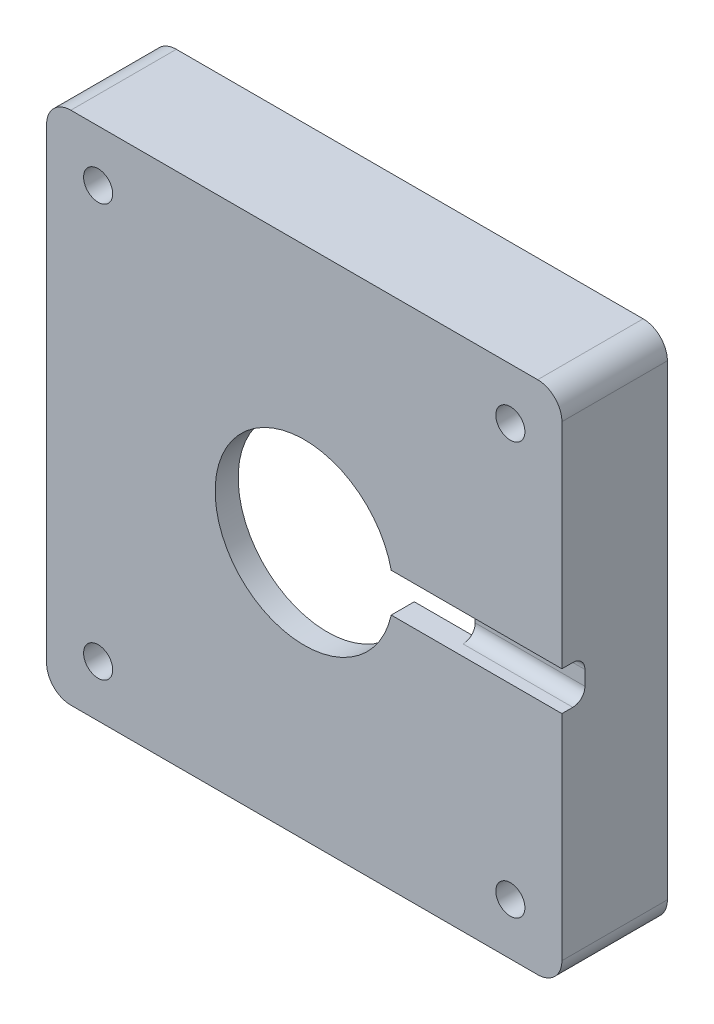
SolidWorks part; units mm, degrees
ref_plane "Front Plane" through (0, 0, 0) normal (0, 0, 1) x (1, 0, 0)
ref_plane "Top Plane" through (0, 0, 0) normal (0, 1, 0) x (1, 0, 0)
ref_plane "Right Plane" through (0, 0, 0) normal (1, 0, 0) x (0, 0, -1)
sketch "Sketch1" plane through (0, 0, 0) normal (0, 0, 1) x (1, 0, 0)
  line L0 (21.25, -19.25) -> (21.25, 19.25) construction
  line L1 (-19.25, -21.25) -> (19.25, -21.25) construction
  line L2 (-21.25, 19.25) -> (-21.25, -19.25) construction
  line L3 (19.25, 21.25) -> (-19.25, 21.25) construction
  line L4 (21.25, -19.25) -> (21.25, 19.25)
  line L5 (-19.25, -21.25) -> (19.25, -21.25)
  line L6 (-21.25, 19.25) -> (-21.25, -19.25)
  line L7 (19.25, 21.25) -> (-19.25, 21.25)
  arc A0 (21.25, 19.25) -> (19.25, 21.25) centre (19.25, 19.25) ccw construction
  arc A1 (19.25, -21.25) -> (21.25, -19.25) centre (19.25, -19.25) ccw construction
  arc A2 (-21.25, -19.25) -> (-19.25, -21.25) centre (-19.25, -19.25) ccw construction
  arc A3 (-19.25, 21.25) -> (-21.25, 19.25) centre (-19.25, 19.25) ccw construction
  arc A4 (21.25, 19.25) -> (19.25, 21.25) centre (19.25, 19.25) ccw
  arc A5 (19.25, -21.25) -> (21.25, -19.25) centre (19.25, -19.25) ccw
  arc A6 (-21.25, -19.25) -> (-19.25, -21.25) centre (-19.25, -19.25) ccw
  arc A7 (-19.25, 21.25) -> (-21.25, 19.25) centre (-19.25, 19.25) ccw
  circle A8 centre (-17, -17) radius 1.2 construction
  circle A9 centre (17, -17) radius 1.2 construction
  circle A10 centre (17, 17) radius 1.2 construction
  circle A11 centre (-17, 17) radius 1.2 construction
  circle A12 centre (-17, -17) radius 1.2
  circle A13 centre (17, -17) radius 1.2
  circle A14 centre (17, 17) radius 1.2
  circle A15 centre (-17, 17) radius 1.2
  point P37 (0.1087, 0)
  point P38 (0, 0)
  point P39 (21.25, 1.6)
extrude "Boss-Extrude1" add sketch "Sketch1" along normal offset from surface (8.7 mm away) 2 offset beyond the face yes
sketch "Sketch2" plane through (0, 0, 0) normal (0, 0, -1) x (-1, 0, 0)
  line L0 (19.25, -19.25) -> (-19.25, -19.25) construction
  line L2 (-19.25, 19.25) -> (19.25, 19.25) construction
  line L3 (19.25, 19.25) -> (19.25, -19.25) construction
  line L4 (17, 14.55) -> (19.25, 14.55) construction
  line L5 (14.55, 19.25) -> (14.55, 17) construction
  line L6 (-14.55, 17) -> (-14.55, 19.25) construction
  line L7 (-19.25, 14.55) -> (-17, 14.55) construction
  line L8 (-14.55, -19.25) -> (-14.55, -17) construction
  line L9 (-17, -14.55) -> (-19.25, -14.55) construction
  line L10 (19.25, -14.55) -> (17, -14.55) construction
  line L11 (14.55, -17) -> (14.55, -19.25) construction
  line L12 (14.55, -19.25) -> (-14.55, -19.25)
  line L13 (-19.25, -14.55) -> (-19.25, 14.55)
  line L14 (-14.55, 19.25) -> (14.55, 19.25)
  line L15 (19.25, 14.55) -> (19.25, -14.55)
  line L16 (17, 14.55) -> (19.25, 14.55)
  line L17 (14.55, 19.25) -> (14.55, 17)
  line L18 (-14.55, 17) -> (-14.55, 19.25)
  line L19 (-19.25, 14.55) -> (-17, 14.55)
  line L20 (-14.55, -19.25) -> (-14.55, -17)
  line L21 (-17, -14.55) -> (-19.25, -14.55)
  line L22 (19.25, -14.55) -> (17, -14.55)
  line L23 (14.55, -17) -> (14.55, -19.25)
  arc A0 (14.55, 17) -> (17, 14.55) centre (17, 17) ccw construction
  arc A1 (-17, 14.55) -> (-14.55, 17) centre (-17, 17) ccw construction
  arc A2 (-14.55, -17) -> (-17, -14.55) centre (-17, -17) ccw construction
  arc A3 (17, -14.55) -> (14.55, -17) centre (17, -17) ccw construction
  arc A4 (14.55, 17) -> (17, 14.55) centre (17, 17) ccw
  arc A5 (-17, 14.55) -> (-14.55, 17) centre (-17, 17) ccw
  arc A6 (-14.55, -17) -> (-17, -14.55) centre (-17, -17) ccw
  arc A7 (17, -14.55) -> (14.55, -17) centre (17, -17) ccw
extrude "Cut-Extrude2" cut sketch "Sketch2" against normal blind 3
sketch "Sketch3" plane through (0, 0, 3) normal (0, 0, -1) x (-1, 0, 0)
  line L0 (-12, -6) -> (-12, 6) construction
  line L1 (5, -13) -> (-5, -13) construction
  line L2 (12, 6) -> (12, -6) construction
  line L3 (-5, 13) -> (5, 13) construction
  line L4 (-12, -6) -> (-12, 6) construction
  line L5 (5, -13) -> (-5, -13) construction
  line L6 (12, 6) -> (12, -6) construction
  line L7 (-5, 13) -> (5, 13) construction
  line L8 (-12.2, -6) -> (-12.2, 6)
  line L9 (-5, 13.2) -> (5, 13.2)
  line L10 (12.2, 6) -> (12.2, -6)
  line L11 (5, -13.2) -> (-5, -13.2)
  arc A0 (-5, 13) -> (-12, 6) centre (-5, 6) ccw construction
  arc A1 (-12, -6) -> (-5, -13) centre (-5, -6) ccw construction
  arc A2 (5, -13) -> (12, -6) centre (5, -6) ccw construction
  arc A3 (12, 6) -> (5, 13) centre (5, 6) ccw construction
  arc A4 (-5, 13) -> (-12, 6) centre (-5, 6) ccw construction
  arc A5 (-12, -6) -> (-5, -13) centre (-5, -6) ccw construction
  arc A6 (5, -13) -> (12, -6) centre (5, -6) ccw construction
  arc A7 (12, 6) -> (5, 13) centre (5, 6) ccw construction
  arc A8 (-5, 13.2) -> (-12.2, 6) centre (-5, 6) ccw
  arc A9 (12.2, 6) -> (5, 13.2) centre (5, 6) ccw
  arc A10 (5, -13.2) -> (12.2, -6) centre (5, -6) ccw
  arc A11 (-12.2, -6) -> (-5, -13.2) centre (-5, -6) ccw
  dimension "D1" = 0.2
extrude "Cut-Extrude3" cut sketch "Sketch3" against normal blind 3.8
sketch "Sketch4" plane through (0, 0, 8.7) normal (0, 0, 1) x (1, 0, 0)
  line L3 (7.0308, -1.3) -> (7.95, -1.3)
  line L4 (7.95, -1.3) -> (7.95, 1.3)
  line L5 (7.95, 1.3) -> (7.0308, 1.3)
  line L9 (7.95, -1.3) -> (7.95, 1.3) construction
  line L10 (8.15, -1.5) -> (8.15, 1.5) construction
  line L11 (8.15, 1.5) -> (7.1953, 1.5) construction
  line L12 (7.95, 1.3) -> (7.0308, 1.3) construction
  line L13 (7.0308, -1.3) -> (7.95, -1.3) construction
  line L14 (7.1953, -1.5) -> (8.15, -1.5) construction
  line L15 (21.25, 19.25) -> (21.25, -19.25) construction
  line L16 (21.25, 1.6) -> (7.1737, 1.6)
  line L17 (21.25, 1.6) -> (21.25, -1.6)
  line L18 (21.25, -1.6) -> (7.1737, -1.6)
  line L21 (21.25, 0) -> (0, 0) construction
  arc A0 (7.1737, 1.6) -> (7.1737, -1.6) centre (0, 0) ccw
  arc A1 (7.0308, 1.3) -> (7.0308, -1.3) centre (0, 0) ccw
  arc A2 (7.0308, 1.3) -> (7.0308, -1.3) centre (0, 0) ccw construction
  arc A3 (7.1953, 1.5) -> (7.1953, -1.5) centre (0, 0) ccw construction
  point P11 (0.2004, 0)
  point P14 (21.25, -1.6)
  point P17 (9.9603, 1.5)
  point P19 (0, 0)
  dimension "D3" = 3.2
  dimension "D1" = 0
  dimension "D2" = 0.2
extrude "Cut-Extrude4" cut sketch "Sketch4" against normal up to surface (1.9 mm away) up to face at (0, 0, 6.8)
sketch "Sketch5" plane through (0, 0, 0) normal (0, 0, -1) x (-1, 0, 0)
  line L0 (-19.25, 14.55) -> (-19.25, -14.55) construction
  line L1 (-19.25, -11.05) -> (-20.25, -11.05)
  line L2 (-19.25, -11.05) -> (-19.25, -9.55)
  line L3 (-19.25, -9.55) -> (-20.25, -9.55)
  line L4 (-20.25, -11.05) -> (-20.25, -9.55)
  line L5 (-19.75, -9.55) -> (-19.75, -11.05) construction
  line L6 (-19.25, -10.3) -> (-20.25, -10.3) construction
  point P4 (-19.25, -9.55)
  point P356 (-19.75, -10.3)
  dimension "D1" = 8
  dimension "D2" = 1.5
  dimension "D3" = 1
extrude "Cut-Extrude5" cut sketch "Sketch5" against normal up to surface (3 mm away) up to face at (0, 0, 3)
fillet "Fillet1" radius 1 4 edges at (19.25, -11.05, 1.5) (19.25, -9.55, 1.5) (16.725, -1.6, 6.8) (16.725, 1.6, 6.8)
